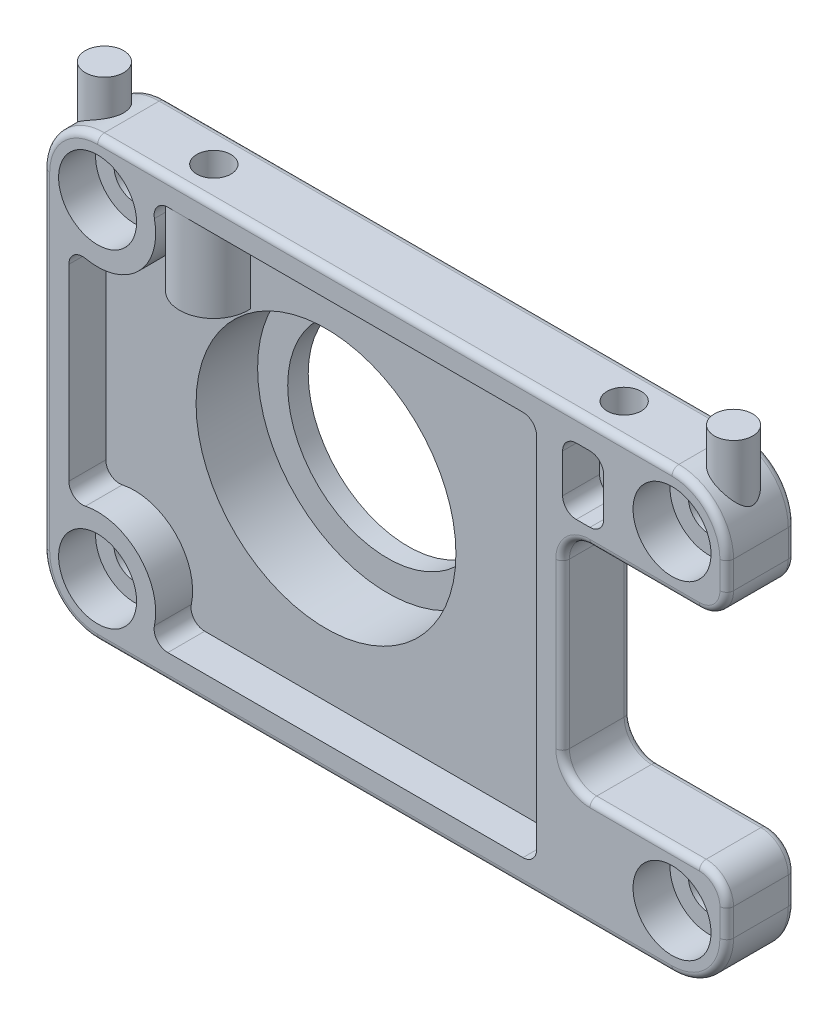
SolidWorks part; units mm, degrees
ref_plane "前视基准面" through (0, 0, 0) normal (0, 0, 1) x (1, 0, 0)
ref_plane "上视基准面" through (0, 0, 0) normal (0, 1, 0) x (1, 0, 0)
ref_plane "右视基准面" through (0, 0, 0) normal (1, 0, 0) x (0, 0, -1)
sketch "草图1" plane through (0, 0, 0) normal (0, 0, 1) x (1, 0, 0)
  line L0 (0, 16) -> (50, 16) construction
  line L1 (0, 0) -> (50, 0)
  line L2 (0, 0) -> (0, 32)
  line L3 (0, 32) -> (50, 32)
  line L4 (50, 0) -> (50, 8)
  line L5 (50, 24) -> (38, 24)
  line L6 (38, 24) -> (38, 8)
  line L7 (50, 8) -> (38, 8)
  line L8 (50, 24) -> (50, 32)
  circle A0 centre (4, 28) radius 1.5
  circle A1 centre (46, 28) radius 1.5
  circle A2 centre (46, 4) radius 1.5
  circle A3 centre (4, 4) radius 1.5
  circle A4 centre (18, 16) radius 9.5
  point P22 (38, 16)
  dimension "D3" = 3
  dimension "D10" = 18
  dimension "D11" = 19
  dimension "D1" = 50
  dimension "D2" = 32
  dimension "D6" = 4
  dimension "D7" = 4
  dimension "D8" = 4
  dimension "D9" = 4
  dimension "D12" = 8
  dimension "D13" = 12
  dimension "D4" = 2
  dimension "D5" = 2
extrude "凸台-拉伸1" add sketch "草图1" along normal blind 5
sketch "草图2" plane through (0, 0, 5) normal (0, 0, 1) x (1, 0, 0)
  line L0 (38, 8) -> (38, 24) construction
  line L1 (38, 25.2613) -> (41, 25.2613)
  line L2 (38, 25.2613) -> (38, 30.1)
  line L3 (36.1, 1.9) -> (36.1, 30.1)
  line L4 (7.6949, 1.9) -> (36.1, 1.9)
  line L5 (36.1, 30.1) -> (7.6949, 30.1)
  line L6 (38, 30.1) -> (41, 30.1)
  line L7 (41, 25.2613) -> (41, 30.1)
  line L24 (1.9, 24.3051) -> (1.9, 7.6949)
  circle A0 centre (4, 28) radius 1.5 construction
  circle A1 centre (4, 28) radius 1.5 construction
  circle A2 centre (4, 4) radius 1.5 construction
  circle A3 centre (4, 4) radius 1.5 construction
  circle A4 centre (46, 28) radius 1.5 construction
  circle A5 centre (46, 28) radius 1.5 construction
  circle A6 centre (46, 4) radius 1.5 construction
  circle A7 centre (46, 4) radius 1.5 construction
  circle A8 centre (4, 28) radius 2.85
  circle A9 centre (4, 4) radius 2.85
  circle A10 centre (46, 4) radius 2.85
  circle A11 centre (46, 28) radius 2.85
  arc A12 (1.9, 24.3051) -> (7.6949, 30.1) centre (4, 28) ccw
  circle A15 centre (4, 28) radius 4.25 construction
  arc A16 (7.6949, 1.9) -> (1.9, 7.6949) centre (4, 4) ccw
  dimension "D4" = 3
  dimension "D2" = 1.35
  dimension "D3" = 1.35
  dimension "D5" = 1.4
extrude "切除-拉伸1" cut sketch "草图2" against normal blind 2.7
fillet "圆角1" radius 1 10 edges at (41, 25.2613, 3.65) (41, 30.1, 3.65) (38, 30.1, 3.65) (38, 25.2613, 3.65) (36.1, 1.9, 3.65) (7.6949, 30.1, 3.65) (1.9, 24.3051, 3.65) (1.9, 7.6949, 3.65) (7.6949, 1.9, 3.65) (36.1, 30.1, 3.65)
fillet "圆角2" radius 4 4 edges at (0, 0, 2.5) (0, 32, 2.5) (50, 0, 2.5) (50, 32, 2.5)
fillet "圆角3" radius 2 4 edges at (38, 24, 2.5) (38, 8, 2.5) (50, 8, 2.5) (50, 24, 2.5)
sketch "草图3" plane through (0, 0, 0) normal (0, 0, -1) x (-1, 0, 0)
  circle A0 centre (-18, 16) radius 11.75
  circle A1 centre (-18, 16) radius 9.5 construction
  circle A2 centre (-18, 16) radius 9.5
  dimension "D1" = 23.5
extrude "凸台-拉伸2" add sketch "草图3" along normal blind 2.2
sketch "草图4" plane through (0, 0, -2.2) normal (0, 0, -1) x (-1, 0, 0)
  circle A0 centre (-18, 16) radius 11.75 construction
  circle A1 centre (-18, 16) radius 11.75
  circle A2 centre (-18, 16) radius 7.3
  dimension "D1" = 14.6
extrude "凸台-拉伸3" add sketch "草图4" along normal blind 1.5
fillet "圆角4" radius 0.5 1 edges at (6.25, 16, -3.7)
fillet "圆角5" radius 0.5 16 edges at (38.5858, 23.4142, 0) (38, 16, 0) (38.5858, 8.5858, 0) (44, 8, 0) (49.4142, 7.4142, 0) (50, 5, 0) (48.8284, 1.1716, 0) (25, 0, 0) (1.1716, 1.1716, 0) (0, 16, 0) (1.1716, 30.8284, 0) (25, 32, 0) (48.8284, 30.8284, 0) (50, 27, 0) (49.4142, 24.5858, 0) (44, 24, 0)
ref_plane "基准面1" through (0, -2.5, 0) normal (0, -1, 0) x (-1, 0, 0)
ref_plane "基准面2" through (25, 0, 0) normal (1, 0, 0) x (0, 0, -1)
sketch "草图5" plane through (0, -2.5, 0) normal (0, -1, 0) x (-1, 0, 0)
  line L0 (-50, -2.5) -> (-36.9904, -2.5) construction
  line L2 (-25, -5) -> (-25, 0) construction
  line L3 (-25, 2.475) -> (-25, -2.475) construction
  line L4 (-50, -5) -> (-46, -5) construction
  line L6 (-4, -5) -> (-46, -5) construction
  line L7 (-46, 0) -> (-4, 0) construction
  circle A0 centre (-48, -2.5) radius 1.4
  dimension "D1" = 2.8
  dimension "D3" = 2.5
  dimension "D2" = 23
extrude "凸台-拉伸5" [suppressed] add sketch "草图5" against normal up to surface (3.0359 mm away)
mirror "镜向3" [suppressed] about plane through (25, 0, 0) normal (1, 0, 0)
sketch "草图8" plane through (0, 1.9, 0) normal (0, 1, 0) x (1, 0, 0)
  line L0 (9.1335, -5) -> (35.1, -5) construction
  line L1 (46, 0) -> (4, 0) construction
  line L3 (9.1335, -2.3) -> (35.1, -2.3) construction
  line L4 (7.508, -2.3) -> (12.492, -2.3)
  arc A0 (7.508, -2.3) -> (12.492, -2.3) centre (10, -2.5) ccw
  dimension "D1" = 10
extrude "凸台-拉伸6" [suppressed] add sketch "草图8" along normal blind 6
hole_wizard "M3 螺纹孔2" [suppressed] positions "草图10" profile "草图9" tap size "M3" standard "Gb"
sketch "草图10" plane through (0, 0, 0) normal (0, -1, 0) x (-1, 0, 0)
  line L4 (-25, -2.5) -> (-10, -2.5) construction
  line L5 (-25, 0) -> (-25, -5) construction
  line L6 (-4, 0) -> (-46, 0) construction
  line L7 (-46, -5) -> (-4, -5) construction
  point P10 (-10, -2.5)
  point P12 (-40, -2.5)
  dimension "D1" = 30
sketch "草图9" plane through (10, 0, 2.5) normal (1, 0, 0) x (0, 0, -1)
  line L0 (0, 0) -> (0, 6.7511)
  line L1 (0, 6.7511) -> (1.25, 6)
  line L2 (1.25, 6) -> (1.25, 0)
  line L5 (1.25, 0) -> (0, 0)
  line L10 (0, 6.7511) -> (-1.25, 6) construction
  line L11 (0, -6.35) -> (0, 107.95) construction
  dimension "螺纹孔钻头直径" = 2.5
  dimension "螺纹孔钻头深度" = 6
  dimension "导头角度" = 118
cosmetic thread "孔螺蚊线2" [suppressed] parameters "D1"=4, "D2"=3
cosmetic thread "孔螺蚊线3" [suppressed] parameters "D1"=4, "D2"=3
ref_plane "基准面3" through (0, 16, 0) normal (0, -1, 0) x (-1, 0, 0)
sketch "草图11" plane through (0, 32, 0) normal (0, 1, 0) x (1, 0, 0)
  line L2 (12.492, -2.3) -> (7.508, -2.3)
  arc A2 (7.508, -2.3) -> (12.492, -2.3) centre (10, -2.5) ccw
  dimension "D1" = 10
extrude "凸台-拉伸7" add sketch "草图11" against normal blind 8
hole_wizard "M3 螺纹孔3" positions "草图13" profile "草图12" tap size "M3" standard "Gb"
sketch "草图13" plane through (0, 32, 0) normal (0, 1, 0) x (1, 0, 0)
  arc A0 (7.508, -2.3) -> (12.492, -2.3) centre (10, -2.5) ccw construction
  arc A1 (7.508, -2.3) -> (12.492, -2.3) centre (10, -2.5) ccw construction
  point P1 (10, -2.5)
  point P6 (40, -2.5)
  dimension "D1" = 30
sketch "草图12" plane through (10, 32, 2.5) normal (1, 0, 0) x (0, 0, 1)
  line L0 (0, 0) -> (0, 6.2511)
  line L1 (0, 6.2511) -> (1.25, 5.5)
  line L2 (1.25, 5.5) -> (1.25, 0)
  line L5 (1.25, 0) -> (0, 0)
  line L10 (0, 6.2511) -> (-1.25, 5.5) construction
  line L11 (0, -6.35) -> (0, 107.95) construction
  dimension "螺纹孔钻头直径" = 2.5
  dimension "螺纹孔钻头深度" = 5.5
  dimension "导头角度" = 118
cosmetic thread "孔螺蚊线4" parameters "D1"=4, "D2"=3
cosmetic thread "孔螺蚊线5" parameters "D1"=4, "D2"=3
fillet "圆角6" radius 0.5 16 edges at (1.1716, 1.1716, 5) (0, 16, 5) (1.1716, 30.8284, 5) (25, 32, 5) (48.8284, 30.8284, 5) (50, 27, 5) (49.4142, 24.5858, 5) (44, 24, 5) (38.5858, 23.4142, 5) (38, 16, 5) (38.5858, 8.5858, 5) (44, 8, 5) (49.4142, 7.4142, 5) (50, 5, 5) (48.8284, 1.1716, 5) (25, 0, 5)
ref_plane "基准面4" through (0, 34.5, 0) normal (0, 1, 0) x (1, 0, 0)
sketch "草图14" plane through (0, 34.5, 0) normal (0, 1, 0) x (1, 0, 0)
  line L1 (0, -2.5) -> (5.731, -2.5) construction
  line L2 (0, -4.5) -> (0, -0.5) construction
  line L3 (25, -2.2) -> (25, 2.2) construction
  circle A0 centre (2, -2.5) radius 1.4
  dimension "D1" = 2.8
  dimension "D2" = 23
extrude "凸台-拉伸8" add sketch "草图14" against normal up to surface (3.0359 mm away) up to face at (1.5858, 30.4142, 2.5)
mirror "镜向7" about plane through (25, 0, 0) normal (1, 0, 0) of "凸台-拉伸8"
